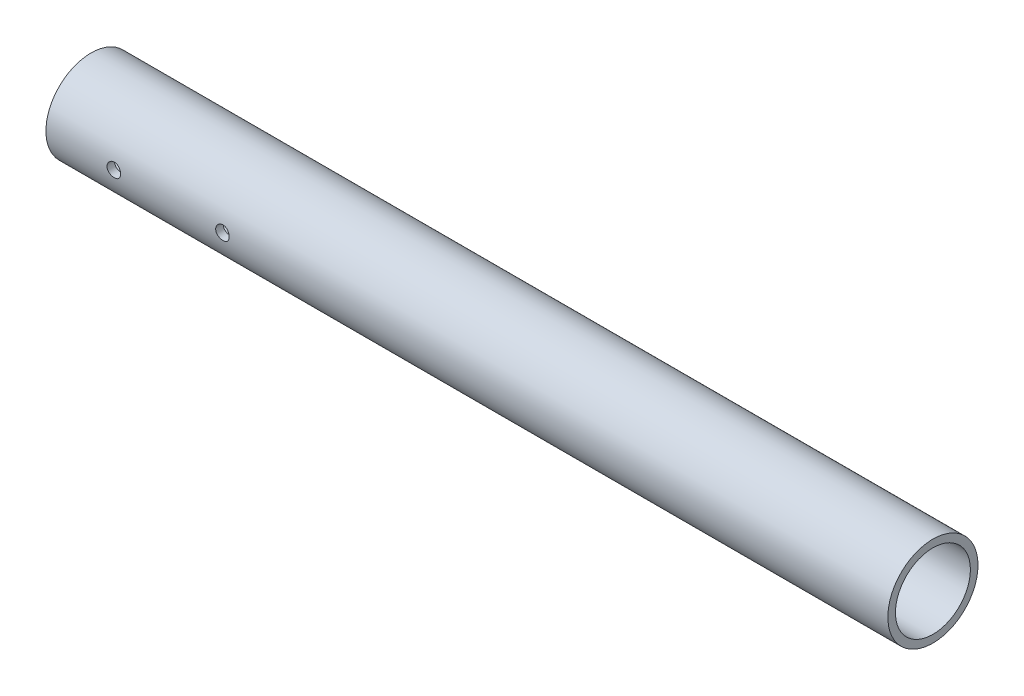
SolidWorks part; units mm, degrees
material "6061-T6 (SS)"
ref_plane "Front Plane" through (0, 0, 0) normal (0, 0, 1) x (1, 0, 0)
ref_plane "Top Plane" through (0, 0, 0) normal (0, 1, 0) x (1, 0, 0)
ref_plane "Right Plane" through (0, 0, 0) normal (1, 0, 0) x (0, 0, -1)
sketch "Sketch1" plane through (0, 0, 0) normal (1, 0, 0) x (0, 0, -1)
  circle A0 centre (0, 0) radius 21.082
  circle A1 centre (0, 0) radius 17.526
  dimension "D1" = 42.164
  dimension "D2" = 35.052
extrude "Boss-Extrude1" add sketch "Sketch1" along normal blind 196.85 and the other way blind 196.85
sketch "Sketch2" plane through (0, 0, 0) normal (0, 0, 1) x (1, 0, 0)
  line L0 (-196.85, 21.082) -> (-196.85, -21.082) construction
  circle A0 centre (-114.3, 0) radius 3.175
  circle A1 centre (-165.1, 0) radius 3.175
  dimension "D1" = 6.35
  dimension "D2" = 31.75
  dimension "D3" = 50.8
extrude "Cut-Extrude1" cut sketch "Sketch2" against normal through all both and the other way through all
